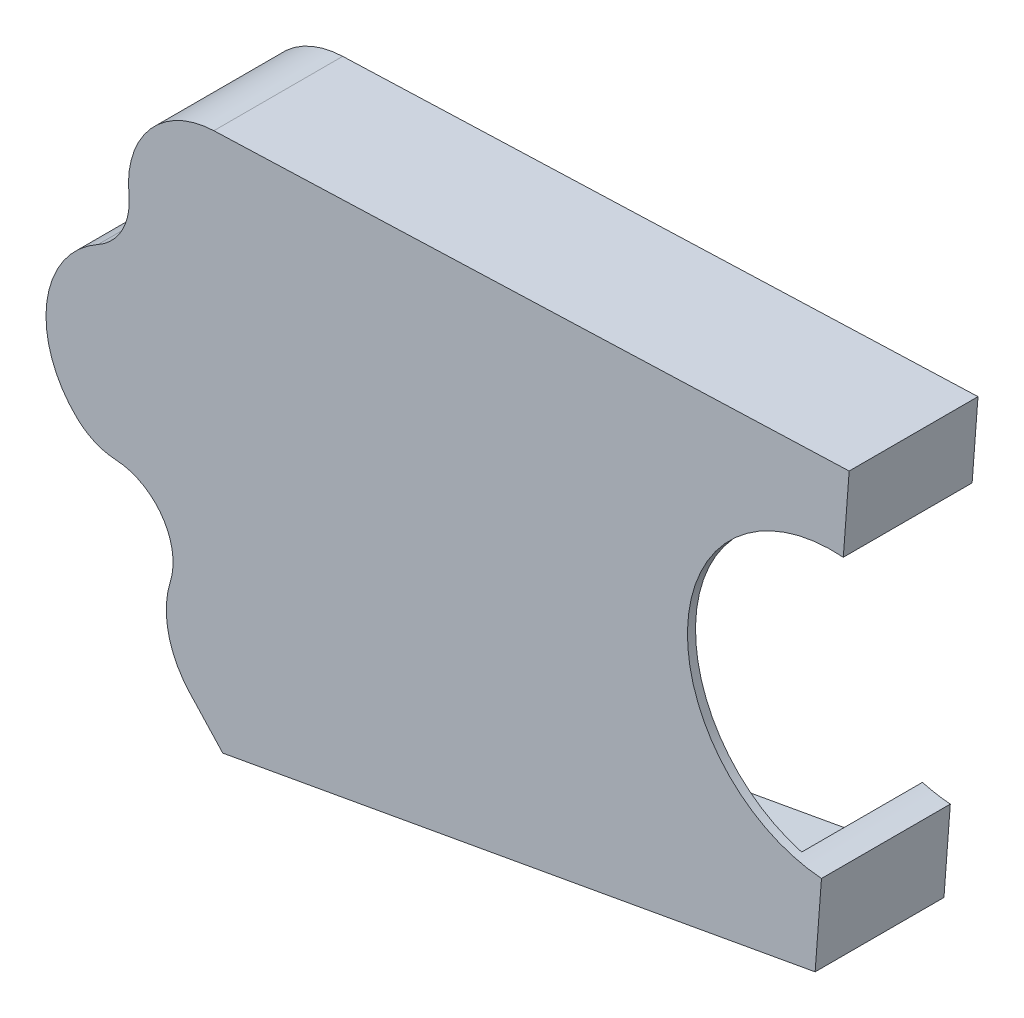
SolidWorks part; units mm, degrees
ref_plane "Front Plane" through (0, 0, 0) normal (0, 0, 1) x (1, 0, 0)
ref_plane "Top Plane" through (0, 0, 0) normal (0, 1, 0) x (1, 0, 0)
ref_plane "Right Plane" through (0, 0, 0) normal (1, 0, 0) x (0, 0, -1)
sketch "Sketch1" plane through (0, 0, 0) normal (0, 0, 1) x (1, 0, 0)
  line L8 (-119.5948, -74.4106) -> (-92.5405, -103.7404)
  line L9 (-119.5948, -74.4106) -> (-92.5405, -103.7404)
  line L10 (-71.3446, -104.5958) -> (-37.2211, -73.1197)
  line L11 (-71.3446, -104.5958) -> (-37.2211, -73.1197)
  line L16 (-27.1401, -68.1042) -> (68.9251, -50.7959)
  line L17 (-111.4072, -83.2869) -> (68.9251, -50.7959)
  line L18 (56.0883, 55.6165) -> (-113.6124, 49.4857)
  line L19 (56.0883, 55.6165) -> (-113.6124, 49.4857)
  line L20 (-114.4495, -69.6645) -> (-87.3952, -98.9943)
  line L21 (-114.4495, -69.6645) -> (-87.3952, -98.9943)
  line L22 (-76.0907, -99.4505) -> (-41.9673, -67.9744)
  line L23 (-76.0907, -99.4505) -> (-41.9673, -67.9744)
  line L28 (-28.3813, -61.2151) -> (67.6838, -43.9068)
  line L29 (-108.8671, -75.7165) -> (67.6838, -43.9068)
  line L30 (56.341, 48.621) -> (-113.3597, 42.4902)
  line L31 (56.341, 48.621) -> (-113.3597, 42.4902)
  line L32 (44.1846, 55.1864) -> (35.7309, -56.7765)
  line L33 (-27.1401, -68.1042) -> (68.9251, -50.7959) construction
  line L34 (-113.6124, 49.4857) -> (56.0883, 55.6165) construction
  line L35 (-111.6252, 43.3) -> (42.409, 31.6699) construction
  line L36 (36.6151, 47.9084) -> (29.1586, -50.848)
  arc A22 (-124.4228, -52.9336) -> (-137.9704, -33.4802) centre (-138.7403, -48.4604) ccw
  arc A23 (-124.4228, -52.9336) -> (-137.9704, -33.4802) centre (-138.7403, -48.4604) ccw
  arc A24 (-124.4228, -52.9336) -> (-119.5948, -74.4106) centre (-103.4238, -59.4942) ccw
  arc A25 (-124.4228, -52.9336) -> (-119.5948, -74.4106) centre (-103.4238, -59.4942) ccw
  arc A26 (-92.5405, -103.7404) -> (-71.3446, -104.5958) centre (-81.5148, -93.5701) ccw
  arc A27 (-92.5405, -103.7404) -> (-71.3446, -104.5958) centre (-81.5148, -93.5701) ccw
  arc A28 (-27.1401, -68.1042) -> (-37.2211, -73.1197) centre (-23.5699, -87.9191) ccw
  arc A29 (-27.1401, -68.1042) -> (-37.2211, -73.1197) centre (-23.5699, -87.9191) ccw
  arc A30 (68.9251, -50.7959) -> (91, -33.5) centre (63.6055, -21.2712) ccw
  arc A31 (68.9251, -50.7959) -> (91, -33.5) centre (63.6055, -21.2712) ccw
  arc A32 (91, -33.5) -> (80.2612, 44.7896) centre (22.6589, -2.9929) ccw
  arc A44 (91, -33.5) -> (80.2612, 44.7896) centre (22.6589, -2.9929) ccw
  arc A45 (80.2612, 44.7896) -> (56.0883, 55.6165) centre (57.1714, 25.636) ccw
  arc A46 (80.2612, 44.7896) -> (56.0883, 55.6165) centre (57.1714, 25.636) ccw
  arc A47 (-113.6124, 49.4857) -> (-134.7058, 25.2795) centre (-112.8181, 27.5) ccw
  arc A48 (-113.6124, 49.4857) -> (-134.7058, 25.2795) centre (-112.8181, 27.5) ccw
  arc A49 (-142.3827, 10.6321) -> (-134.7058, 25.2795) centre (-149.6292, 23.7656) ccw
  arc A50 (-142.3827, 10.6321) -> (-134.7058, 25.2795) centre (-149.6292, 23.7656) ccw
  arc A51 (-142.3827, 10.6321) -> (-147.5429, -29.3643) centre (-130.3054, -11.2571) ccw
  arc A52 (-142.3827, 10.6321) -> (-147.5429, -29.3643) centre (-130.3054, -11.2571) ccw
  arc A53 (-147.5429, -29.3643) -> (-137.9704, -33.4802) centre (-137.2004, -18.5) ccw
  arc A54 (-147.5429, -29.3643) -> (-137.9704, -33.4802) centre (-137.2004, -18.5) ccw
  arc A55 (-117.7413, -55.0211) -> (-137.611, -26.4895) centre (-138.7403, -48.4604) ccw
  arc A56 (-117.7413, -55.0211) -> (-137.611, -26.4895) centre (-138.7403, -48.4604) ccw
  arc A57 (-117.7413, -55.0211) -> (-114.4495, -69.6645) centre (-103.4238, -59.4942) ccw
  arc A58 (-117.7413, -55.0211) -> (-114.4495, -69.6645) centre (-103.4238, -59.4942) ccw
  arc A59 (-87.3952, -98.9943) -> (-76.0907, -99.4505) centre (-81.5148, -93.5701) ccw
  arc A60 (-87.3952, -98.9943) -> (-76.0907, -99.4505) centre (-81.5148, -93.5701) ccw
  arc A61 (-28.3813, -61.2151) -> (-41.9673, -67.9744) centre (-23.5699, -87.9191) ccw
  arc A62 (-28.3813, -61.2151) -> (-41.9673, -67.9744) centre (-23.5699, -87.9191) ccw
  arc A63 (67.6838, -43.9068) -> (84.608, -30.6466) centre (63.6055, -21.2712) ccw
  arc A73 (67.6838, -43.9068) -> (84.608, -30.6466) centre (63.6055, -21.2712) ccw
  arc A74 (84.608, -30.6466) -> (74.8736, 40.3204) centre (22.6589, -2.9929) ccw
  arc A75 (84.608, -30.6466) -> (74.8736, 40.3204) centre (22.6589, -2.9929) ccw
  arc A76 (74.8736, 40.3204) -> (56.341, 48.621) centre (57.1714, 25.636) ccw
  arc A77 (74.8736, 40.3204) -> (56.341, 48.621) centre (57.1714, 25.636) ccw
  arc A78 (-113.3597, 42.4902) -> (-127.7415, 25.986) centre (-112.8181, 27.5) ccw
  arc A79 (-113.3597, 42.4902) -> (-127.7415, 25.986) centre (-112.8181, 27.5) ccw
  arc A80 (-139.0011, 4.5031) -> (-127.7415, 25.986) centre (-149.6292, 23.7656) ccw
  arc A81 (-139.0011, 4.5031) -> (-127.7415, 25.986) centre (-149.6292, 23.7656) ccw
  arc A82 (-139.0011, 4.5031) -> (-142.7164, -24.2943) centre (-130.3054, -11.2571) ccw
  arc A83 (-139.0011, 4.5031) -> (-142.7164, -24.2943) centre (-130.3054, -11.2571) ccw
  arc A84 (-142.7164, -24.2943) -> (-137.611, -26.4895) centre (-137.2004, -18.5) ccw
  arc A85 (-142.7164, -24.2943) -> (-137.611, -26.4895) centre (-137.2004, -18.5) ccw
  circle A86 centre (40.0178, 0) radius 36
  arc A87 (48.7175, 33.9015) -> (14.6094, 24.0711) centre (40.0178, 0) ccw construction
  dimension "D4" = 1
  dimension "D3" = 7
  dimension "D1" = 0
  dimension "D2" = 7
extrude "Boss-Extrude1" add sketch "Sketch1" along normal blind 30 contours A52 A54 A23 A25 L9 A27 L11 A29 L17 A31 A44 A46 L19 A48 A50 A85 A83 A81 A79 L31 A77 A75 A73 L29 A62 L23 A60 L21 A58 A56 | A62 L29 L21 L17 L23 | L29 A62 L23 L17 L32 | A86 L36 L29 L32 | A86 L32 L31 L36 region at (-122.5189, -63.7868, 0) region at (-72.9993, -72.6407, 0) region at (-2.1687, -60.1476, 0) region at (33.1772, -42.8072, 0) region at (39.6825, 41.9847, 0)
sketch "Sketch3" plane through (0, 0, 30) normal (0, 0, 1) x (1, 0, 0)
  line L0 (-65.2656, 44.2277) -> (121.4688, -34.2162)
  line L1 (-113.3597, 42.4902) -> (36.6151, 47.9084) construction
  line L2 (29.1586, -50.848) -> (-108.8671, -75.7165) construction
  dimension "D1" = 33
sketch "Sketch4" plane through (0, 0, 30) normal (0, 0, 1) x (1, 0, 0)
  line L21 (-113.3597, 42.4902) -> (36.6151, 47.9084)
  line L22 (36.6151, 47.9084) -> (35.6963, 35.7397)
  line L23 (42.7282, 35.8978) -> (44.1846, 55.1864)
  line L24 (44.1846, 55.1864) -> (-113.6124, 49.4857)
  line L25 (-119.5948, -74.4106) -> (-111.4072, -83.2869)
  line L26 (-111.4072, -83.2869) -> (35.7309, -56.7765)
  line L27 (35.7309, -56.7765) -> (37.3074, -35.8978)
  line L28 (30.379, -34.6856) -> (29.1586, -50.848)
  line L29 (29.1586, -50.848) -> (-108.8671, -75.7165)
  line L30 (-108.8671, -75.7165) -> (-114.4495, -69.6645)
  line L31 (-113.3597, 42.4902) -> (36.6151, 47.9084)
  line L32 (36.6151, 47.9084) -> (35.6963, 35.7397)
  line L33 (42.7282, 35.8978) -> (44.1846, 55.1864)
  line L34 (44.1846, 55.1864) -> (-113.6124, 49.4857)
  line L35 (-119.5948, -74.4106) -> (-111.4072, -83.2869)
  line L36 (-111.4072, -83.2869) -> (35.7309, -56.7765)
  line L37 (35.7309, -56.7765) -> (37.3074, -35.8978)
  line L38 (30.379, -34.6856) -> (29.1586, -50.848)
  line L39 (29.1586, -50.848) -> (-108.8671, -75.7165)
  line L40 (-108.8671, -75.7165) -> (-114.4495, -69.6645)
  circle A14 centre (40.0178, 0) radius 36
  arc A28 (-142.7164, -24.2943) -> (-137.611, -26.4895) centre (-137.2004, -18.5) ccw
  arc A29 (-139.0011, 4.5031) -> (-142.7164, -24.2943) centre (-130.3054, -11.2571) ccw
  arc A30 (-139.0011, 4.5031) -> (-127.7415, 25.986) centre (-149.6292, 23.7656) ccw
  arc A31 (-113.3597, 42.4902) -> (-127.7415, 25.986) centre (-112.8181, 27.5) ccw
  arc A32 (42.7282, 35.8978) -> (35.6963, 35.7397) centre (40.0178, 0) ccw
  arc A33 (-113.6124, 49.4857) -> (-134.7058, 25.2795) centre (-112.8181, 27.5) ccw
  arc A34 (-142.3827, 10.6321) -> (-134.7058, 25.2795) centre (-149.6292, 23.7656) ccw
  arc A35 (-142.3827, 10.6321) -> (-147.5429, -29.3643) centre (-130.3054, -11.2571) ccw
  arc A36 (-147.5429, -29.3643) -> (-137.9704, -33.4802) centre (-137.2004, -18.5) ccw
  arc A37 (-124.4228, -52.9336) -> (-137.9704, -33.4802) centre (-138.7403, -48.4604) ccw
  arc A38 (-124.4228, -52.9336) -> (-119.5948, -74.4106) centre (-103.4238, -59.4942) ccw
  arc A39 (30.379, -34.6856) -> (37.3074, -35.8978) centre (40.0178, 0) ccw
  arc A40 (-117.7413, -55.0211) -> (-114.4495, -69.6645) centre (-103.4238, -59.4942) ccw
  arc A41 (-117.7413, -55.0211) -> (-137.611, -26.4895) centre (-138.7403, -48.4604) ccw
  arc A42 (-142.7164, -24.2943) -> (-137.611, -26.4895) centre (-137.2004, -18.5) ccw
  arc A43 (-139.0011, 4.5031) -> (-142.7164, -24.2943) centre (-130.3054, -11.2571) ccw
  arc A44 (-139.0011, 4.5031) -> (-127.7415, 25.986) centre (-149.6292, 23.7656) ccw
  arc A45 (-113.3597, 42.4902) -> (-127.7415, 25.986) centre (-112.8181, 27.5) ccw
  arc A46 (42.7282, 35.8978) -> (35.6963, 35.7397) centre (40.0178, 0) ccw
  arc A47 (-113.6124, 49.4857) -> (-134.7058, 25.2795) centre (-112.8181, 27.5) ccw
  arc A48 (-142.3827, 10.6321) -> (-134.7058, 25.2795) centre (-149.6292, 23.7656) ccw
  arc A49 (-142.3827, 10.6321) -> (-147.5429, -29.3643) centre (-130.3054, -11.2571) ccw
  arc A50 (-147.5429, -29.3643) -> (-137.9704, -33.4802) centre (-137.2004, -18.5) ccw
  arc A51 (-124.4228, -52.9336) -> (-137.9704, -33.4802) centre (-138.7403, -48.4604) ccw
  arc A52 (-124.4228, -52.9336) -> (-119.5948, -74.4106) centre (-103.4238, -59.4942) ccw
  arc A53 (30.379, -34.6856) -> (37.3074, -35.8978) centre (40.0178, 0) ccw
  arc A54 (-117.7413, -55.0211) -> (-114.4495, -69.6645) centre (-103.4238, -59.4942) ccw
  arc A55 (-117.7413, -55.0211) -> (-137.611, -26.4895) centre (-138.7403, -48.4604) ccw
  arc M25 (-137.611, -26.4895) -> (-142.7164, -24.2943) centre (-137.2004, -18.5) cw
  arc M26 (-142.7164, -24.2943) -> (-139.0011, 4.5031) centre (-130.3054, -11.2571) cw
  arc M27 (-139.0011, 4.5031) -> (-127.7415, 25.986) centre (-149.6292, 23.7656) ccw
  arc M28 (-127.7415, 25.986) -> (-113.3597, 42.4902) centre (-112.8181, 27.5) cw
  line M29 (-113.3597, 42.4902) -> (36.6151, 47.9084)
  line M30 (36.6151, 47.9084) -> (35.6963, 35.7397)
  arc M31 (35.6963, 35.7397) -> (42.7282, 35.8978) centre (40.0178, 0) cw
  line M32 (42.7282, 35.8978) -> (44.1846, 55.1864)
  line M33 (44.1846, 55.1864) -> (-113.6124, 49.4857)
  arc M34 (-113.6124, 49.4857) -> (-134.7058, 25.2795) centre (-112.8181, 27.5) ccw
  arc M35 (-134.7058, 25.2795) -> (-142.3827, 10.6321) centre (-149.6292, 23.7656) cw
  arc M36 (-142.3827, 10.6321) -> (-147.5429, -29.3643) centre (-130.3054, -11.2571) ccw
  arc M37 (-147.5429, -29.3643) -> (-137.9704, -33.4802) centre (-137.2004, -18.5) ccw
  arc M38 (-137.9704, -33.4802) -> (-124.4228, -52.9336) centre (-138.7403, -48.4604) cw
  arc M39 (-124.4228, -52.9336) -> (-119.5948, -74.4106) centre (-103.4238, -59.4942) ccw
  line M40 (-119.5948, -74.4106) -> (-111.4072, -83.2869)
  line M41 (-111.4072, -83.2869) -> (35.7309, -56.7765)
  line M42 (35.7309, -56.7765) -> (37.3074, -35.8978)
  arc M43 (37.3074, -35.8978) -> (30.379, -34.6856) centre (40.0178, 0) cw
  line M44 (30.379, -34.6856) -> (29.1586, -50.848)
  line M45 (29.1586, -50.848) -> (-108.8671, -75.7165)
  line M46 (-108.8671, -75.7165) -> (-114.4495, -69.6645)
  arc M47 (-114.4495, -69.6645) -> (-117.7413, -55.0211) centre (-103.4238, -59.4942) cw
  arc M48 (-117.7413, -55.0211) -> (-137.611, -26.4895) centre (-138.7403, -48.4604) ccw
  dimension "D1" = 0
extrude "Boss-Extrude2" add sketch "Sketch4" along normal blind 2 contours A14 M30 M29 M28 M27 M26 M25 M48 M47 M46 M45 M44 | M48 M25 M26 M27 M28 M29 M30 M31 M32 M33 M34 M35 M36 M37 M38 M39 M40 M41 M42 M43 M44 M45 M46 M47 region at (-125.9577, 38.9499, 30) region at (-57.9317, -9.5661, 30)
